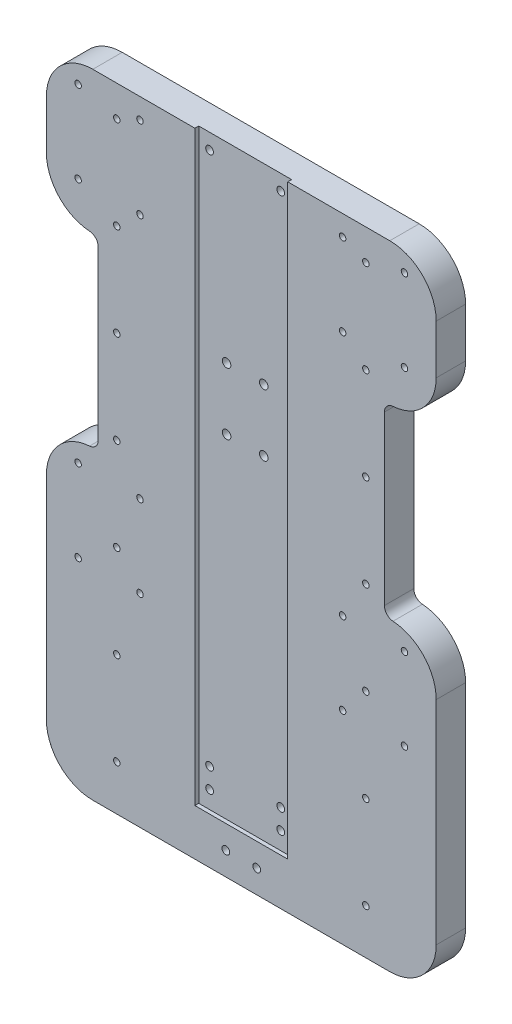
SolidWorks part; units mm, degrees
ref_plane "Piano frontale" through (0, 0, 0) normal (0, 0, 1) x (1, 0, 0)
ref_plane "Piano superiore" through (0, 0, 0) normal (0, 1, 0) x (1, 0, 0)
ref_plane "Piano destro" through (0, 0, 0) normal (1, 0, 0) x (0, 0, -1)
sketch "Schizzo1" plane through (0, 0, 0) normal (0, 0, 1) x (1, 0, 0)
  line L1 (126, -250) -> (-126, -250)
  line L2 (126, -250) -> (126, 250)
  line L3 (126, 250) -> (-126, 250)
  line L4 (-126, -250) -> (-126, 250)
  line L5 (126, -250) -> (-126, 250) construction
  line L6 (126, 250) -> (-126, -250) construction
  point P0 (0, 0)
  dimension "D1" = 252
  dimension "D2" = 500
extrude "Estrusione-Estrusione1" add sketch "Schizzo1" along normal blind 19
sketch "Schizzo2" plane through (0, 0, 19) normal (0, 0, 1) x (1, 0, 0)
  line L0 (1265.2426, 21.4119) -> (-695.7574, 21.4119) construction
  line L1 (1265.2426, 13.5541) -> (-695.7574, 13.5541) construction
  line L2 (1265.2426, 53.5541) -> (-695.7574, 53.5541) construction
  line L3 (1265.2426, 61.4119) -> (-695.7574, 61.4119) construction
  line L4 (-126, 250) -> (-126, -250)
  line L5 (-126, -250) -> (126, -250)
  line L6 (126, -250) -> (126, 250)
  line L7 (126, 250) -> (-126, 250)
  line L8 (-126, 250) -> (-126, -250) construction
  line L9 (-126, -250) -> (126, -250) construction
  line L10 (126, -250) -> (126, 250) construction
  line L11 (126, 250) -> (-126, 250) construction
  line L12 (1265.2426, 21.4119) -> (-695.7574, 21.4119) construction
  line L13 (1265.2426, 13.5541) -> (-695.7574, 13.5541) construction
  line L14 (1265.2426, 53.5541) -> (-695.7574, 53.5541) construction
  line L15 (1265.2426, 61.4119) -> (-695.7574, 61.4119) construction
  line L16 (126, -45.017) -> (-126, -45.017) construction
  line L17 (126, -25.017) -> (-126, -25.017) construction
  line L18 (126, -45.017) -> (-126, -45.017) construction
  line L19 (126, -25.017) -> (-126, -25.017) construction
  line L20 (-126, -45.017) -> (-126, -25.017) construction
  line L21 (126, -35.017) -> (-126, -35.017) construction
  line L22 (-126, -45.017) -> (126, -45.017) construction
  line L23 (-126, -45.017) -> (-126, -25.017) construction
  line L24 (-126, -25.017) -> (126, -25.017) construction
  line L25 (126, -45.017) -> (126, -25.017) construction
  circle A0 centre (110, 17.483) radius 3.9289
  circle A1 centre (110, 57.483) radius 3.9289
  circle A2 centre (-110, 17.483) radius 3.9289
  circle A3 centre (-110, 57.483) radius 3.9289
  circle A4 centre (110, -35.017) radius 3.5
  circle A5 centre (-110, -35.017) radius 3.5
  circle A6 centre (55, -35.017) radius 3.5
  circle A8 centre (-55, -35.017) radius 3.5
  circle A9 centre (20, -35.017) radius 3.5
  circle A10 centre (-20, -35.017) radius 3.5
  circle A11 centre (165, -35.017) radius 3.5 [skipped]
  dimension "D2" = 16
  dimension "D3" = 7.8579
  dimension "D4" = 16
  dimension "D5" = 7.8579
  dimension "D6" = 7
  dimension "D7" = 7
  dimension "D8" = 2
  dimension "D1" = 0
  dimension "D9" = 2
  dimension "D10" = 2
  dimension "D11" = 2
sketch "Schizzo3" plane through (0, 250, 0) normal (0, 1, 0) x (1, 0, 0)
  line L0 (126, -19) -> (-126, -19) construction
  line L1 (30, -16.5) -> (-30, -16.5)
  line L2 (30, -16.5) -> (30, -19)
  line L3 (30, -19) -> (-30, -19)
  line L4 (-30, -16.5) -> (-30, -19)
  line L5 (126, -19) -> (126, 0) construction
  line L6 (-126, -19) -> (-126, 0) construction
  line L7 (126, -19) -> (-126, -19) construction
  dimension "D1" = 2.5
  dimension "D2" = 96
  dimension "D3" = 96
extrude "Taglio-Estrusione1" cut sketch "Schizzo3" against normal through all
sketch "Schizzo4" plane through (0, 0, 16.5) normal (0, 0, 1) x (1, 0, 0)
  line L0 (30, -250) -> (30, 250) construction
  line L2 (30, 250) -> (-30, 250) construction
  line L3 (30, -250) -> (30, 250) construction
  line L6 (-30, 250) -> (-126, 250) construction
  line L7 (-30, -250) -> (-30, 250) construction
  point P11 (23, -118)
  point P14 (-23, -118)
  point P15 (-23, -105)
  point P16 (23, -105)
  point P17 (23, 240)
  point P18 (-23, 240)
  dimension "D1" = 46
  dimension "D2" = 13
  dimension "D3" = 13
  dimension "D4" = 46
  dimension "D5" = 7
  dimension "D6" = 345
  dimension "D7" = 10
  dimension "D8" = 46
  dimension "D9" = 7
  dimension "D10" = 10
  dimension "D11" = 7
  dimension "D12" = 7
sketch "Schizzo5" plane through (0, 0, 19) normal (0, 0, 1) x (1, 0, 0)
  point P4 (80.5006, 170)
  point P7 (80.5006, 110)
  point P16 (80.5006, 50)
  point P17 (80.5006, -10)
  point P18 (80.5006, -70)
  point P19 (80.5006, -130)
  point P20 (80.5006, 230)
hole_wizard "Tap Drill for M5 Tap2" positions "Sketch7" profile "Sketch8" hole size "M5" standard "ISO"
sketch "Sketch7" plane through (0, 0, 19) normal (0, 0, 1) x (1, 0, 0)
  point P0 (80.5006, -130)
  point P3 (80.5006, -70)
  point P7 (80.5006, -10)
  point P10 (80.5006, 50)
  point P13 (80.5006, 110)
  point P16 (80.5006, 170)
  point P19 (80.5006, 230)
sketch "Sketch8" plane through (80.5006, -130, 19) normal (1, 0, 0) x (0, -1, 0)
  line L0 (0, 0) -> (0, 37.8618)
  line L1 (0, 37.8618) -> (2.1, 36.6)
  line L2 (2.1, 36.6) -> (2.1, 0)
  line L5 (2.1, 0) -> (0, 0)
  line L10 (0, 37.8618) -> (-2.1, 36.6) construction
  line L11 (0, -6.35) -> (0, 107.95) construction
  dimension "Hole Dia." = 4.2
  dimension "Hole Depth" = 36.6
  dimension "Drill Angle" = 118
sketch "Schizzo6" plane through (0, 0, 19) normal (0, 0, 1) x (1, 0, 0)
  line L0 (126, -250) -> (126, 250) construction
  line L2 (126, 250) -> (30, 250) construction
  point P23 (108, 172.8083)
  point P26 (63, 172.8083)
  point P27 (63, 229.8083)
  point P28 (108, 229.8083)
  dimension "D1" = 45
  dimension "D2" = 45
  dimension "D3" = 57
  dimension "D4" = 57
  dimension "D5" = 18
  dimension "D6" = 20.1917
  dimension "D7" = 20.1917
  dimension "D8" = 18
hole_wizard "Tap Drill for M5 Tap1" positions "Sketch14" profile "Sketch15" hole size "M5" standard "ISO"
sketch "Sketch14" plane through (0, 0, 19) normal (0, 0, 1) x (1, 0, 0)
  line L1 (105.5, 183.8083) -> (65.5, 183.8083)
  line L2 (105.5, 183.8083) -> (105.5, 236.8083)
  line L3 (105.5, 236.8083) -> (65.5, 236.8083)
  line L4 (65.5, 183.8083) -> (65.5, 236.8083)
  line L6 (105.5, -28.1917) -> (65.5, -28.1917)
  line L7 (105.5, -28.1917) -> (105.5, 24.8083)
  line L8 (105.5, 24.8083) -> (65.5, 24.8083)
  line L9 (65.5, -28.1917) -> (65.5, 24.8083)
  line L10 (85.5, -28.1917) -> (85.5, 236.8083) construction
  line L12 (105.5, 210.3083) -> (65.5, 210.3083) construction
  line L14 (105.5, -1.6917) -> (65.5, -1.6917) construction
  line L16 (108, 172.8083) -> (63, 172.8083) construction
  line L18 (85.5, 256.2745) -> (85.5, -301.4126) construction
  point P19 (105.5, 236.8083)
  point P21 (65.5, 236.8083)
  point P23 (105.5, 183.8083)
  point P25 (65.5, 183.8083)
  point P99 (105.5, -28.1917)
  point P102 (65.5, -28.1917)
  point P105 (65.5, 24.8083)
  point P108 (105.5, 24.8083)
  dimension "D1" = 40
  dimension "D2" = 53
  dimension "D3" = 40
  dimension "D4" = 53
sketch "Sketch15" plane through (105.5, 236.8083, 19) normal (1, 0, 0) x (0, -1, 0)
  line L0 (0, 0) -> (0, 37.8618)
  line L1 (0, 37.8618) -> (2.1, 36.6)
  line L2 (2.1, 36.6) -> (2.1, 0)
  line L5 (2.1, 0) -> (0, 0)
  line L10 (0, 37.8618) -> (-2.1, 36.6) construction
  line L11 (0, -6.35) -> (0, 107.95) construction
  dimension "Hole Dia." = 4.2
  dimension "Hole Depth" = 36.6
  dimension "Drill Angle" = 118
hole_wizard "Tap Drill for M6 Tap4" positions "Sketch9" profile "Sketch10" hole size "M6" standard "ISO"
sketch "Sketch9" plane through (0, 0, 16.5) normal (0, 0, 1) x (1, 0, 0)
  point P0 (23, -118)
  point P3 (23, -105)
  point P6 (-23, -118)
  point P9 (-23, -105)
  point P12 (23, 240)
  point P15 (-23, 240)
sketch "Sketch10" plane through (23, -118, 16.5) normal (1, 0, 0) x (0, -1, 0)
  line L0 (0, 0) -> (0, 38.1022)
  line L1 (0, 38.1022) -> (2.5, 36.6)
  line L2 (2.5, 36.6) -> (2.5, 0)
  line L5 (2.5, 0) -> (0, 0)
  line L10 (0, 38.1022) -> (-2.5, 36.6) construction
  line L11 (0, -6.35) -> (0, 107.95) construction
  dimension "Hole Dia." = 5
  dimension "Hole Depth" = 36.6
  dimension "Drill Angle" = 118
sketch "Sketch11" plane through (0, 0, 16.5) normal (0, 0, 1) x (1, 0, 0)
  line L0 (0, -250) -> (0, 250) construction
  line L1 (30, -250) -> (-30, -250) construction
  line L2 (30, 250) -> (-30, 250) construction
ref_plane "Plane1" through (0, 0, 0) normal (-1, 0, 0) x (0, 0, 1)
mirror "Mirror1" about plane through (0, 0, 0) normal (-1, 0, 0) of "Tap Drill for M5 Tap2"
mirror "Mirror2" about plane through (0, 0, 0) normal (-1, 0, 0) of "Tap Drill for M5 Tap1"
sketch "Sketch16" plane through (0, 0, 0) normal (0, 0, -1) x (-1, 0, 0)
  line L0 (126, 250) -> (126, -250) construction
  line L1 (126, -317.9299) -> (-126, -317.9299)
  line L2 (126, -317.9299) -> (126, -159.25)
  line L3 (126, -159.25) -> (-126, -159.25)
  line L4 (-126, -317.9299) -> (-126, -159.25)
  line L5 (-126, -250) -> (-126, 250) construction
  line L9 (-12.9, -159.25) -> (25.2, -159.25) construction
extrude "Cut-Extrude1" cut sketch "Sketch16" against normal blind 28
sketch "Sketch26" plane through (0, 0, 16.5) normal (0, 0, 1) x (1, 0, 0)
  line L0 (30, -159.25) -> (30, 250) construction
  line L1 (-30, -159.25) -> (30, -159.25)
  line L2 (-30, -159.25) -> (-30, -129.25)
  line L3 (-30, -129.25) -> (30, -129.25)
  line L4 (30, -159.25) -> (30, -129.25)
  dimension "D1" = 30
extrude "Boss-Extrude1" add sketch "Sketch26" along normal up to surface (2.5 mm away) up to face at (-78, 45.375, 19)
hole_wizard "M5 Clearance Hole1" positions "Sketch17" profile "Sketch18" hole size "M5" standard "ISO" end condition through all
sketch "Sketch17" plane through (0, 0, 16.5) normal (0, 0, 1) x (1, 0, 0)
  line L0 (12, 86.3083) -> (-12, 126.3083) construction
  line L1 (-12, 126.3083) -> (-12, 86.3083) construction
  line L2 (-12, 86.3083) -> (12, 126.3083) construction
  line L3 (12, 126.3083) -> (12, 86.3083) construction
  line L4 (12, 86.3083) -> (-12, 86.3083) construction
  line L7 (-12, 126.3083) -> (12, 126.3083) construction
  point P0 (-12, 86.3083)
  point P2 (12, 86.3083)
  point P4 (12, 126.3083)
  point P6 (-12, 126.3083)
  dimension "D1" = 40
  dimension "D2" = 24
sketch "Sketch18" plane through (-12, 86.3083, 16.5) normal (1, 0, 0) x (0, -1, 0)
  line L0 (0, 0) -> (0, 16.5)
  line L1 (0, 16.5) -> (2.75, 16.5)
  line L2 (2.75, 16.5) -> (2.75, 0)
  line L5 (2.75, 0) -> (0, 0)
  line L11 (0, -6.35) -> (0, 107.95) construction
  dimension "Thru Hole Dia." = 5.5
  dimension "Thru Hole Depth" = 16.5
sketch "Sketch19" plane through (0, -195.45, 0) normal (0, -1, 0) x (-1, 0, 0)
  line L0 (0, -70.7) -> (0, 68.239) construction
  line L1 (126, -9.5) -> (-126, -9.5) construction
  line L2 (126, -19) -> (126, 0) construction
  line L3 (-126, -19) -> (-126, 0) construction
  line L5 (28.2, 0) -> (-28.2, 0) construction
  point P8 (20, -9.5)
  point P9 (-20, -9.5)
  point P12 (-20, 9.5)
  point P13 (20, 9.5)
  dimension "D1" = 20
hole_wizard "Tap Drill for M6 Tap2" positions "Sketch22" profile "Sketch23" hole size "M6" standard "ISO"
sketch "Sketch22" plane through (0, -159.25, 0) normal (0, -1, 0) x (-1, 0, 0)
  point P0 (20, -7.125)
  point P2 (-20, -7.125)
sketch "Sketch23" plane through (-20, -159.25, 7.125) normal (1, 0, 0) x (0, 0, -1)
  line L0 (0, 0) -> (0, 31.5022)
  line L1 (0, 31.5022) -> (2.5, 30)
  line L2 (2.5, 30) -> (2.5, 0)
  line L5 (2.5, 0) -> (0, 0)
  line L10 (0, 31.5022) -> (-2.5, 30) construction
  line L11 (0, -6.35) -> (0, 107.95) construction
  dimension "Hole Dia." = 5
  dimension "Hole Depth" = 30
  dimension "Drill Angle" = 118
hole_wizard "Tap Drill for M6 Tap3" positions "Sketch24" profile "Sketch25" hole size "M6" standard "ISO" end condition through all
sketch "Sketch24" plane through (0, 0, 0) normal (0, 0, -1) x (-1, 0, 0)
  point P0 (-10, -144.25)
  point P6 (10, -144.25)
sketch "Sketch25" plane through (10, -144.25, 0) normal (1, 0, 0) x (0, 1, 0)
  line L0 (0, 0) -> (0, 19)
  line L1 (0, 19) -> (2.5, 19)
  line L2 (2.5, 19) -> (2.5, 0)
  line L5 (2.5, 0) -> (0, 0)
  line L11 (0, -6.35) -> (0, 107.95) construction
  dimension "Thru Hole Dia." = 5
  dimension "Thru Hole Depth" = 19
sketch "Sketch27" plane through (0, 0, 19) normal (0, 0, 1) x (1, 0, 0)
  line L2 (-126, 38.082) -> (-126, 158.222)
  line L4 (-92.5, 38.082) -> (-92.5, 158.222)
  line L5 (-126, 38.082) -> (-92.5, 38.082)
  line L7 (-126, 158.222) -> (-92.5, 158.222)
  line L9 (-92.5, 40.082) -> (-92.5, 156.222) construction
  line L10 (-126, 40.082) -> (-126, 156.222) construction
  line L11 (-128, 158.222) -> (-90.5, 158.222) construction
  line L12 (-128, 38.082) -> (-128, 158.222) construction
  line L13 (-128, 38.082) -> (-90.5, 38.082) construction
  line L14 (-126, 40.082) -> (-92.5, 40.082) construction
  line L15 (-90.5, 38.082) -> (-90.5, 158.222) construction
  line L16 (-126, 156.222) -> (-92.5, 156.222) construction
  line L17 (-126, 98.152) -> (126, 98.152) construction
  line L18 (126, -159.25) -> (126, 250) construction
  line L19 (126, 98.152) -> (0, 98.152) construction
  line L20 (0, 98.152) -> (0, 87.9155) construction
  line L21 (-126, 38.082) -> (-92.5, 38.082)
  line L22 (-126, 158.222) -> (-92.5, 158.222)
  line L23 (126, 158.222) -> (92.5, 158.222)
  line L24 (126, 38.082) -> (92.5, 38.082)
  line L25 (126, 158.222) -> (92.5, 158.222)
  line L26 (126, 38.082) -> (92.5, 38.082)
  line L27 (92.5, 38.082) -> (92.5, 158.222)
  line L28 (126, 38.082) -> (126, 158.222)
  line M11 (-126, 250) -> (-126, -159.25)
  line M13 (126, -159.25) -> (126, 250)
  dimension "D1" = 2
extrude "Cut-Extrude2" cut sketch "Sketch27" against normal blind 76.9911 contours L27 L24 L23 M13 | L7 L5 L4 M11 region at (-109.25, 98.152, 19) region at (109.25, 98.152, 19)
fillet "Fillet1" radius 30 4 edges at (126, 158.222, 9.5) (126, 38.082, 9.5) (-126, 158.222, 9.5) (-126, 38.082, 9.5)
fillet "Fillet2" radius 30 4 edges at (126, 250, 9.5) (-126, 250, 9.5) (-126, -159.25, 9.5) (126, -159.25, 9.5)
fillet "Fillet3" radius 6 4 edges at (92.5, 158.222, 9.5) (92.5, 38.082, 9.5) (-92.5, 38.082, 9.5) (-92.5, 158.222, 9.5)
sketch "Sketch28" plane through (0, 0, 0) normal (0, 0, -1) x (-1, 0, 0)
  line L0 (-32, 106.3083) -> (32, 106.3083) construction
  line L4 (32, 78.3083) -> (-32, 78.3083)
  line L5 (32, 78.3083) -> (32, 134.3083)
  line L6 (32, 134.3083) -> (-32, 134.3083)
  line L7 (-32, 78.3083) -> (-32, 134.3083)
  line L8 (0, -10.45) -> (0, 10.45) construction
  circle A0 centre (-12, 86.3083) radius 2.75 construction
  circle A1 centre (-12, 86.3083) radius 2.75 construction
  dimension "D4" = 32
  dimension "D1" = 32
  dimension "D2" = 28
extrude "Cut-Extrude3" cut sketch "Sketch28" against normal blind 2
sketch "Sketch29" plane through (0, 0, 2) normal (0, 0, -1) x (-1, 0, 0)
  line L0 (12, 86.3083) -> (12, 79.3083) construction
  line L1 (-17.5, 82.3083) -> (17.5, 82.3083)
  line L2 (-17.5, 82.3083) -> (-17.5, 130.3083)
  line L3 (-17.5, 130.3083) -> (17.5, 130.3083)
  line L4 (17.5, 82.3083) -> (17.5, 130.3083)
  circle A0 centre (12, 86.3083) radius 2.6
  circle A1 centre (-12, 86.3083) radius 2.6
  circle A2 centre (12, 126.3083) radius 2.6
  circle A3 centre (-12, 126.3083) radius 2.6
  circle A4 centre (12, 79.3083) radius 0.5
  circle A5 centre (-12, 79.3083) radius 0.5
  circle A6 centre (12, 119.3083) radius 0.5
  circle A7 centre (-12, 119.3083) radius 0.5
  dimension "D1" = 5.2
  dimension "D2" = 5.2
  dimension "D3" = 5.2
  dimension "D4" = 5.2
  dimension "D5" = 1
  dimension "D6" = 1
  dimension "D7" = 1
  dimension "D8" = 1
  dimension "D9" = 7
equation "\"D3@Schizzo3\"=\"D2@Schizzo3\""
equation "\"D11@Schizzo4\"=\"D5@Schizzo4\""
